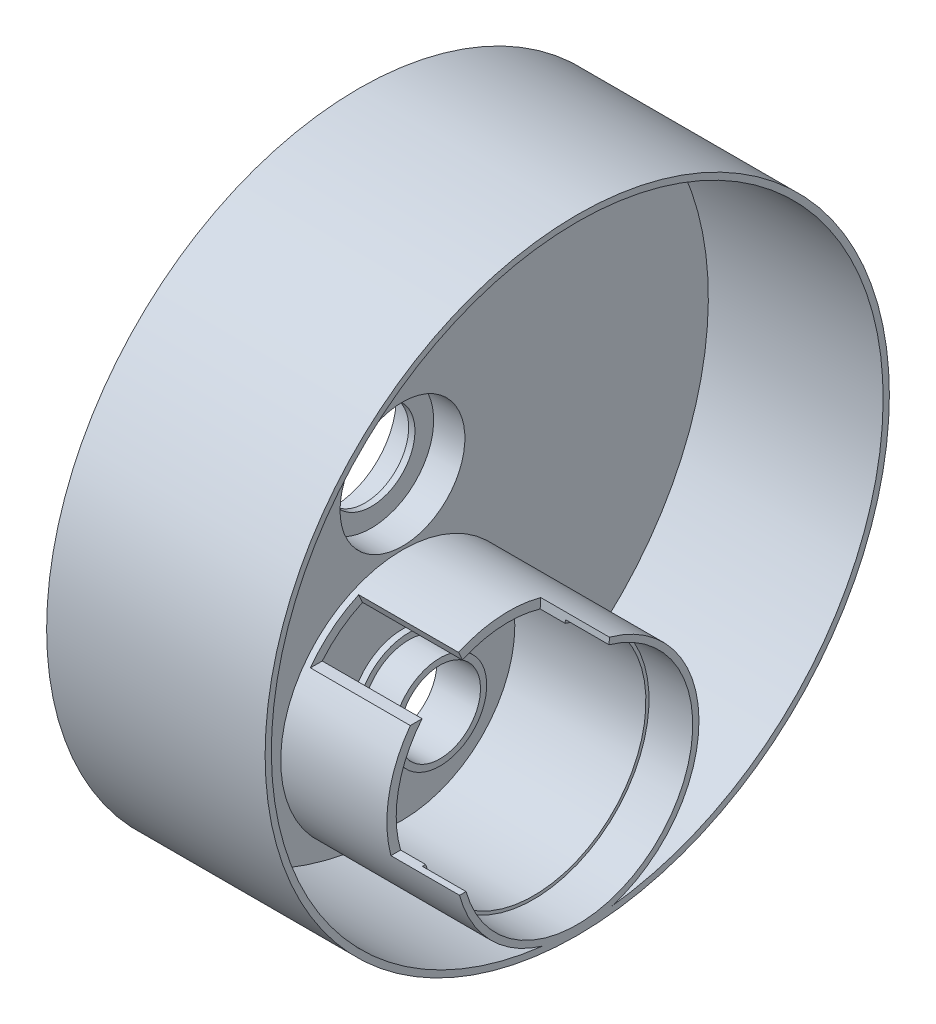
SolidWorks part; units mm, degrees
material "1060 Сплав"
ref_plane "Спереди" through (0, 0, 0) normal (0, 0, 1) x (1, 0, 0)
ref_plane "Сверху" through (0, 0, 0) normal (0, 1, 0) x (1, 0, 0)
ref_plane "Справа" through (0, 0, 0) normal (1, 0, 0) x (0, 0, -1)
sketch "Эскиз1" plane through (0, 0, 0) normal (0, 0, 1) x (1, 0, 0)
  line L0 (0, 0) -> (26039.5549, 0) construction
  line L1 (-27, 7.5) -> (-27, 8.5)
  line L2 (0, 19.5) -> (-29, 19.5)
  line L3 (-29, 19.5) -> (-29, 6.5)
  line L4 (-29, 6.5) -> (-22, 6.5)
  line L5 (-22, 6.5) -> (-22, 7.5)
  line L6 (-22, 7.5) -> (-27, 7.5)
  line L7 (-28, 8.5) -> (-28, 18)
  line L8 (-28, 18) -> (-7, 18)
  line L9 (-7, 18) -> (-7, 18.5)
  line L10 (-7, 18.5) -> (0, 18.5)
  line L11 (0, 18.5) -> (0, 19.5)
  line L12 (-27, 8.5) -> (-28, 8.5)
  dimension "D1" = 18.5
  dimension "D2" = 1
  dimension "D3" = 18
  dimension "D4" = 7
  dimension "D5" = 21
  dimension "D6" = 1
  dimension "D7" = 1
  dimension "D8" = 1
  dimension "D9" = 7.5
  dimension "D10" = 1
  dimension "D11" = 13
  dimension "D12" = 0.5
  dimension "D13" = 5
revolve "Повернуть1" add sketch "Эскиз1" angle 360 about L0
sketch "Эскиз2" plane through (0, 0, 0) normal (1, 0, 0) x (0, 0, -1)
  line L0 (0, 0) -> (0, 50000) construction
  line L1 (5.1563, 18.8059) -> (5, 16.2481)
  line L2 (5, 0) -> (5, 50000) construction
  line L3 (0, 0) -> (0, -5) construction
  line L4 (0, -5) -> (-50000, -5) construction
  line L5 (-18.8481, -5) -> (-16.2481, -5)
  line L6 (-5, 0) -> (-5, 50000) construction
  arc A0 (5, 16.2481) -> (-16.2481, -5) centre (0, 0) ccw
  arc A1 (-18.8481, -5) -> (5.1563, 18.8059) centre (0, 0) cw
  circle A2 centre (0, 0) radius 19.5 construction
  dimension "D3" = 17
  dimension "D4" = 19.5
  dimension "D1" = 5
  dimension "D2" = 5
  dimension "D5" = 2.5626
  dimension "D6" = 0
extrude "Вырез-Вытянуть1" cut sketch "Эскиз2" against normal blind 11 contours A0 L5 A1 L1
sketch "Эскиз3" plane through (0, 0, 0) normal (1, 0, 0) x (0, 0, -1)
  line L3 (-40, 11.5) -> (-12.52, 11.5)
  line L4 (0, 0) -> (-20535.6471, 45588.2353) construction
  line L5 (-6.9821, 15.5) -> (-13.2408, 29.394)
  line L6 (-13.2408, 29.394) -> (-40, 11.5)
  line L7 (0, 15.5) -> (-50000, 15.5) construction
  circle A0 centre (0, 0) radius 15.5 construction
  circle A1 centre (0, 0) radius 11.5 construction
  arc A2 (-6.9821, 15.5) -> (-12.52, 11.5) centre (0, 0) ccw
  dimension "D1" = 31
  dimension "D2" = 23
  dimension "D4" = 34
  dimension "D3" = 15.2386
  dimension "D5" = 32.1908
extrude "Вырез-Вытянуть2" cut sketch "Эскиз3" against normal blind 27
sketch "Эскиз4" plane through (-29, 0, 0) normal (-1, 0, 0) x (0, 0, 1)
  circle A1 centre (0, 30) radius 50
  circle A2 centre (0, 30) radius 10
  circle A3 centre (0, 0) radius 6.5 construction
  circle A4 centre (0, 0) radius 6.5
  dimension "D2" = 100
  dimension "D3" = 20
  dimension "D5" = 13
  dimension "D1" = 30
  dimension "D4" = 30
extrude "Бобышка-Вытянуть1" add sketch "Эскиз4" against normal blind 1
sketch "Эскиз5" plane through (-29, 0, 0) normal (-1, 0, 0) x (0, 0, 1)
  circle A0 centre (0, 30) radius 50
  circle A1 centre (0, 30) radius 49
  dimension "D1" = 100
  dimension "D2" = 98
extrude "Бобышка-Вытянуть2" add sketch "Эскиз5" against normal blind 29 and the other way blind 6
sketch "Эскиз9" plane through (0, 0, 0) normal (0, 0, 1) x (1, 0, 0)
  line L0 (-50.3474, 30) -> (12.875, 30) construction
  line L1 (-39, 40) -> (-34, 40)
  line L2 (-39, 41) -> (-29, 41)
  line L3 (-34, 40) -> (-34, 37)
  line L4 (-34, 37) -> (-33, 37)
  line L5 (-33, 37) -> (-33, 40)
  line L6 (-33, 40) -> (-29, 40)
  line L7 (-29, 40) -> (-29, 41)
  line L8 (-39, 41) -> (-39, 40)
  line L11 (-28, 20) -> (-28, 40) construction
  dimension "D1" = 30
  dimension "D2" = 1
  dimension "D3" = 5
  dimension "D4" = 5
  dimension "D5" = 11
  dimension "D6" = 3
revolve "Повернуть2" add sketch "Эскиз9" angle 360 about L0
